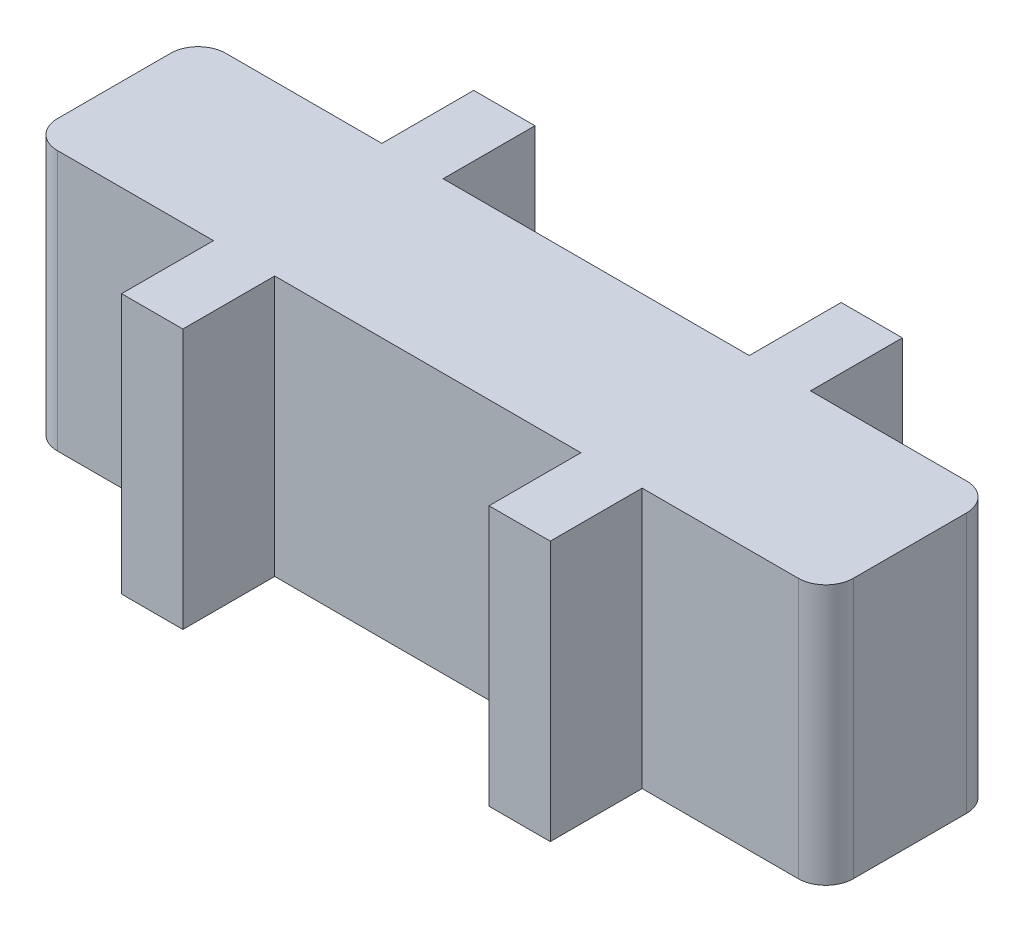
SolidWorks part; units mm, degrees
ref_plane "Front Plane" through (0, 0, 0) normal (0, 0, 1) x (1, 0, 0)
ref_plane "Top Plane" through (0, 0, 0) normal (0, 1, 0) x (1, 0, 0)
ref_plane "Right Plane" through (0, 0, 0) normal (1, 0, 0) x (0, 0, -1)
sketch "Sketch1" plane through (0, 0, 0) normal (0, 1, 0) x (1, 0, 0)
  line L0 (-13, 0) -> (13, 0) construction
  line L1 (-13, -2.75) -> (13, -2.75)
  line L2 (-13, -2.75) -> (-13, 2.75)
  line L3 (-13, 2.75) -> (13, 2.75)
  line L5 (-13, -2.75) -> (0, 0) construction
  line L6 (-13, 2.75) -> (0, 0) construction
  line L7 (0, 2.75) -> (0, -2.75)
  line L8 (-7, -5.75) -> (-5, -5.75)
  line L9 (-7, -5.75) -> (-7, 5.75)
  line L10 (-7, 5.75) -> (-5, 5.75)
  line L11 (-5, -5.75) -> (-5, 5.75)
  line L12 (-7, -5.75) -> (-5, 5.75) construction
  line L13 (-7, 5.75) -> (-5, -5.75) construction
  line L18 (7, 5.75) -> (5, -5.75) construction
  line L19 (7, -5.75) -> (5, 5.75) construction
  line L20 (13, 2.75) -> (0, 0) construction
  line L21 (13, -2.75) -> (0, 0) construction
  line L22 (5, -5.75) -> (5, 5.75)
  line L23 (7, 5.75) -> (5, 5.75)
  line L24 (7, -5.75) -> (7, 5.75)
  line L25 (7, -5.75) -> (5, -5.75)
  line L26 (13, -2.75) -> (13, 2.75)
  point P0 (0, 0)
  point P1 (0, 2.5)
  point P4 (10.2585, -2.5)
  point P7 (-12.7579, -2.5)
  point P8 (-6, 0)
  point P22 (6, 0)
  dimension "D1" = 5
  dimension "D2" = 3
  dimension "D3" = 5.5
  dimension "D4" = 6
  dimension "D5" = 2
extrude "Boss-Extrude1" add sketch "Sketch1" along normal blind 8.5 contours L1 L9 L3 L2 | L3 L11 L10 L9 | L8 L11 L1 L9 | L1 L11 L3 L9 | L11 L1 L7 L3 | L1 L22 L3 L7 | L3 L24 L23 L22 | L1 L26 L3 L24 | L1 L24 L3 L22 | L25 L24 L1 L22 region at (-10, 0, 0) region at (-6, 0, 0) region at (-6, 0, 4.25) region at (-2.5, 0, 0) region at (-6, 0, -4.25) region at (2.5, 0, 0) region at (6, 0, 0) region at (6, 0, 4.25) region at (10, 0, 0) region at (6, 0, -4.25)
fillet "Fillet1" radius 0.9 4 edges at (13, 4.25, -2.75) (13, 4.25, 2.75) (-13, 4.25, 2.75) (-13, 4.25, -2.75)
